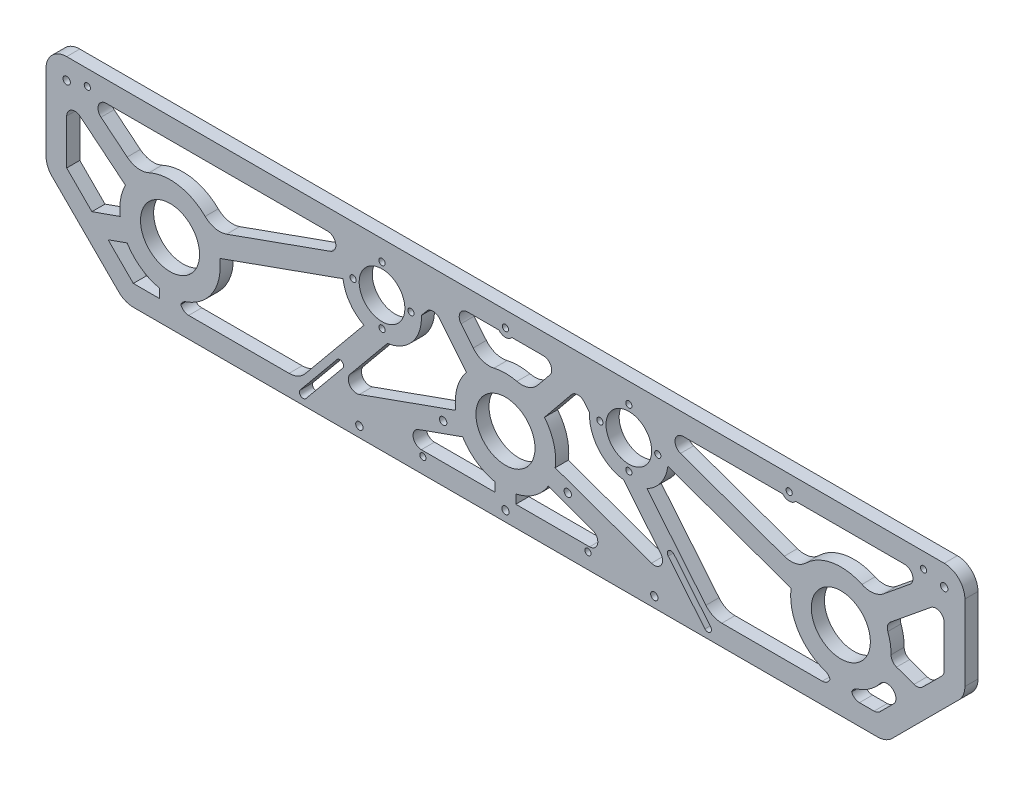
SolidWorks part; units mm, degrees
material "6061 Alloy"
ref_plane "Front Plane" through (0, 0, 0) normal (0, 0, 1) x (1, 0, 0)
ref_plane "Top Plane" through (0, 0, 0) normal (0, 1, 0) x (1, 0, 0)
ref_plane "Right Plane" through (0, 0, 0) normal (1, 0, 0) x (0, 0, -1)
sketch "Sketch1" plane through (0, 0, 0) normal (0, 0, 1) x (1, 0, 0)
  line L0 (2.9289, 35.1711) -> (35.1711, 2.9289)
  line L1 (42.2421, 0) -> (402.2579, 0)
  line L2 (0, 42.2421) -> (0, 78.9)
  line L3 (10, 88.9) -> (434.5, 88.9)
  line L4 (444.5, 42.2421) -> (444.5, 78.9)
  line L5 (409.3289, 2.9289) -> (441.5711, 35.1711)
  line L6 (222.25, 88.9) -> (222.25, 78.9) construction
  line L7 (42.2421, 10) -> (55, 10)
  line L8 (402.2579, 10) -> (414.4609, 22.2031)
  line L9 (434.5, 42.2421) -> (434.5, 72.4466)
  line L10 (17.9086, 78.9) -> (159.3033, 78.9)
  line L11 (10, 42.2421) -> (10, 72.4466)
  line L12 (10, 42.2421) -> (22.2031, 30.0391)
  line L13 (24.4543, 30.8351) -> (22.2031, 30.0391)
  line L14 (30.0391, 22.2031) -> (42.2421, 10)
  line L15 (10, 42.2421) -> (42.2421, 10) construction
  line L16 (44.7466, 57.0002) -> (17.9086, 78.9)
  line L17 (30.0391, 22.2031) -> (39.259, 25.463)
  line L18 (55, 14.3327) -> (55, 10)
  line L19 (38.4244, 49.2523) -> (10, 72.4466)
  line L20 (24.4543, 30.8351) -> (35.9254, 34.891)
  line L21 (65, 14.3327) -> (65, 10)
  line L22 (399.7534, 57.0002) -> (426.5914, 78.9)
  line L23 (65, 10) -> (128.7681, 10)
  line L24 (10, 78.9) -> (434.5, 78.9) construction
  line L25 (42.2421, 10) -> (402.2579, 10) construction
  line L26 (10, 42.2421) -> (10, 78.9) construction
  line L27 (185.1403, 75.7423) -> (203.3633, 53.37)
  line L28 (175.8429, 74.1917) -> (184.0222, 77.1149)
  line L29 (80.6981, 50.8071) -> (159.3033, 78.9)
  line L30 (84.0636, 41.3904) -> (175.8429, 74.1917)
  line L31 (158.4819, 10) -> (201.5519, 25.3929)
  line L32 (141.9423, 14.7083) -> (198.1864, 34.8096)
  line L33 (195.4658, 78.9) -> (211.1167, 59.6855)
  line L34 (185.1403, 75.7423) -> (184.0222, 77.1149)
  line L35 (406.0756, 49.2523) -> (434.5, 72.4466)
  line L36 (195.4658, 78.9) -> (249.0342, 78.9)
  line L37 (158.4819, 10) -> (217.25, 10)
  line L38 (217.25, 14.3327) -> (217.25, 10)
  line L39 (141.9423, 14.7083) -> (128.7681, 10)
  line L40 (420.0457, 30.8351) -> (422.2969, 30.0391)
  line L41 (420.0457, 30.8351) -> (408.5746, 34.891)
  line L42 (379.5, 14.3327) -> (379.5, 10)
  line L43 (389.5, 14.3327) -> (389.5, 10)
  line L44 (414.4609, 22.2031) -> (405.241, 25.463)
  line L45 (414.4609, 22.2031) -> (402.2579, 10)
  line L46 (402.2579, 10) -> (389.5, 10)
  line L47 (379.5, 10) -> (315.7319, 10)
  line L48 (286.0181, 10) -> (227.25, 10)
  line L49 (302.5577, 14.7083) -> (315.7319, 10)
  line L50 (302.5577, 14.7083) -> (246.3136, 34.8096)
  line L51 (286.0181, 10) -> (242.9481, 25.3929)
  line L52 (363.8019, 50.8071) -> (285.1967, 78.9)
  line L53 (360.4364, 41.3904) -> (268.6571, 74.1917)
  line L54 (268.6571, 74.1917) -> (260.4778, 77.1149)
  line L55 (259.3597, 75.7423) -> (260.4778, 77.1149)
  line L56 (249.0342, 78.9) -> (233.3833, 59.6855)
  line L57 (259.3597, 75.7423) -> (241.1367, 53.37)
  line L58 (285.1967, 78.9) -> (426.5914, 78.9)
  line L59 (422.2969, 30.0391) -> (434.5, 42.2421)
  line L60 (402.2579, 10) -> (434.5, 42.2421) construction
  line L61 (434.5, 42.2421) -> (434.5, 78.9) construction
  line L62 (227.25, 10) -> (227.25, 14.3327)
  arc A0 (434.5, 88.9) -> (444.5, 78.9) centre (434.5, 78.9) cw
  arc A1 (441.5711, 35.1711) -> (444.5, 42.2421) centre (434.5, 42.2421) ccw
  arc A2 (409.3289, 2.9289) -> (402.2579, 0) centre (402.2579, 10) cw
  arc A3 (35.1711, 2.9289) -> (42.2421, 0) centre (42.2421, 10) ccw
  arc A4 (2.9289, 35.1711) -> (0, 42.2421) centre (10, 42.2421) cw
  arc A5 (0, 78.9) -> (10, 88.9) centre (10, 78.9) cw
  circle A6 centre (60, 38.1) radius 14.2875
  circle A8 centre (384.5, 38.1) radius 14.2875
  arc A9 (402.2579, 10) -> (402.2579, 10) centre (402.2579, 10) cw
  arc A10 (434.5, 42.2421) -> (434.5, 42.2421) centre (434.5, 42.2421) ccw
  arc A11 (434.5, 78.9) -> (434.5, 78.9) centre (434.5, 78.9) cw
  arc A12 (10, 78.9) -> (10, 78.9) centre (10, 78.9) cw
  arc A13 (10, 42.2421) -> (10, 42.2421) centre (10, 42.2421) cw
  arc A14 (42.2421, 10) -> (42.2421, 10) centre (42.2421, 10) ccw
  arc A15 (38.4244, 49.2523) -> (35.9254, 34.891) centre (60, 38.1) ccw
  arc A16 (201.5519, 25.3929) -> (217.25, 14.3327) centre (222.25, 38.1) ccw
  arc A17 (363.8019, 50.8071) -> (399.7534, 57.0002) centre (384.5, 38.1) cw
  circle A18 centre (60, 38.1) radius 24.2875 construction
  arc A19 (39.259, 25.463) -> (55, 14.3327) centre (60, 38.1) ccw
  arc A20 (65, 14.3327) -> (84.0636, 41.3904) centre (60, 38.1) ccw
  arc A21 (80.6981, 50.8071) -> (44.7466, 57.0002) centre (60, 38.1) ccw
  circle A22 centre (222.25, 38.1) radius 14.2875
  arc A23 (203.3633, 53.37) -> (198.1864, 34.8096) centre (222.25, 38.1) ccw
  arc A24 (227.25, 14.3327) -> (242.9481, 25.3929) centre (222.25, 38.1) ccw
  arc A25 (246.3136, 34.8096) -> (241.1367, 53.37) centre (222.25, 38.1) ccw
  arc A26 (233.3833, 59.6855) -> (211.1167, 59.6855) centre (222.25, 38.1) ccw
  circle A27 centre (384.5, 38.1) radius 24.2875 construction
  arc A28 (406.0756, 49.2523) -> (408.5746, 34.891) centre (384.5, 38.1) cw
  arc A29 (379.5, 14.3327) -> (360.4364, 41.3904) centre (384.5, 38.1) cw
  arc A30 (405.241, 25.463) -> (389.5, 14.3327) centre (384.5, 38.1) cw
  point P0 (0, 0)
  point P3 (444.5, 0)
  point P13 (444.5, 38.1)
  point P16 (406.4, 0)
  point P19 (38.1, 0)
  point P22 (0, 38.1)
  point P25 (0, 88.9)
  dimension "D3" = 10
  dimension "D4" = 28.575
  dimension "D5" = 28.575
  dimension "D1" = 88.9
  dimension "D2" = 444.5
  dimension "D8" = 60
  dimension "D9" = 10
  dimension "D10" = 10
  dimension "D11" = 10
extrude "Boss-Extrude1" add sketch "Sketch1" along normal blind 6.35 contours A5 L2 A4 L0 A3 L1 A2 L5 A1 L4 A0 L3 A30 L44 L8 L46 L43 A29 L42 L47 L49 L50 A25 L57 L55 L54 L53 A28 L35 L9 L59 L40 L41 A22 A17 L52 L58 L22 A6 A8 L19 A15 L20 region at (4.9492, 40.15, 0)
sketch "Sketch2" plane through (0, 0, 6.35) normal (0, 0, 1) x (1, 0, 0)
  line L0 (65, 10) -> (128.7681, 10) construction
  line L1 (128.7681, 10) -> (198.1864, 34.8096) construction
  line L2 (257.2568, 73.1606) -> (306.5554, 13.2796)
  line L3 (174.8458, 73.8353) -> (124.908, 13.178)
  line L4 (269.6542, 73.8353) -> (319.592, 13.178)
  line L5 (187.8824, 73.937) -> (137.9446, 13.2796)
  line L6 (184.0222, 77.1149) -> (203.3633, 53.37) construction
  line L7 (84.0636, 41.3904) -> (184.0222, 77.1149) construction
  line L8 (122.2917, 10) -> (128.7681, 10)
  line L9 (128.7681, 10) -> (137.9446, 13.2796)
  line L10 (184.0222, 77.1149) -> (187.2432, 73.1606)
  line L11 (174.8458, 73.8353) -> (184.0222, 77.1149)
  line L12 (124.908, 13.178) -> (122.2917, 10)
  line L13 (319.592, 13.178) -> (322.2083, 10)
  line L14 (246.3136, 34.8096) -> (315.7319, 10) construction
  line L15 (379.5, 10) -> (315.7319, 10) construction
  line L16 (260.4778, 77.1149) -> (241.1367, 53.37) construction
  line L17 (360.4364, 41.3904) -> (260.4778, 77.1149) construction
  line L18 (306.5554, 13.2796) -> (315.7319, 10)
  line L19 (322.2083, 10) -> (315.7319, 10)
  line L20 (260.4778, 77.1149) -> (257.2568, 73.1606)
  line L21 (269.6542, 73.8353) -> (260.4778, 77.1149)
extrude "Boss-Extrude2" add sketch "Sketch2" against normal up to surface (6.35 mm away) contours L3 L12 L8 L9 L5 L10 L11 | L4 L21 L20 L2 L18 L19 L13 region at (288.5779, 43.0632, 6.35) region at (155.9221, 43.0632, 6.35) up to face at (400.4223, 16.074, 0)
fillet "Fillet1" radius 10 8 edges at (80.6981, 50.8071, 3.175) (44.7466, 57.0002, 3.175) (211.1167, 59.6855, 3.175) (233.3833, 59.6855, 3.175) (122.2917, 10, 3.175) (322.2083, 10, 3.175) (399.7534, 57.0002, 3.175) (363.8019, 50.8071, 3.175)
fillet "Fillet2" radius 4 16 edges at (10, 72.4466, 3.175) (434.5, 72.4466, 3.175) (17.9086, 78.9, 3.175) (159.3033, 78.9, 3.175) (174.8458, 73.8353, 3.175) (269.6542, 73.8353, 3.175) (286.0181, 10, 3.175) (158.4819, 10, 3.175) (137.9446, 13.2796, 3.175) (306.5554, 13.2796, 3.175) (257.2568, 73.1606, 3.175) (187.2432, 73.1606, 3.175) (195.4658, 78.9, 3.175) (249.0342, 78.9, 3.175) (426.5914, 78.9, 3.175) (285.1967, 78.9, 3.175)
fillet "Fillet3" radius 4 13 edges at (434.5, 42.2421, 3.175) (422.2969, 30.0391, 3.175) (408.5746, 34.891, 3.175) (406.0756, 49.2523, 3.175) (414.4609, 22.2031, 3.175) (405.241, 25.463, 3.175) (402.2579, 10, 3.175) (389.5, 10, 3.175) (389.5, 14.3327, 3.175) (65, 10, 3.175) (65, 14.3327, 3.175) (379.5, 14.3327, 3.175) (379.5, 10, 3.175)
sketch "Sketch3" plane through (0, 0, 0) normal (0, 0, -1) x (-1, 0, 0)
  line L0 (-222.25, 88.9) -> (-222.25, 78.9) construction
  line L1 (-10, 88.9) -> (-434.5, 88.9) construction
  line L2 (-203.8829, 78.9) -> (-240.6171, 78.9) construction
  circle A0 centre (-434.5, 78.9) radius 1.778
  circle A2 centre (-252.3834, 27.3306) radius 1.778
  circle A3 centre (-192.1166, 27.3306) radius 1.778
  circle A4 centre (-10, 78.9) radius 1.778
  circle A5 centre (-222.25, 38.1) radius 14.2875 construction
  dimension "D1" = 3.556
  dimension "D2" = 3.556
  dimension "D3" = 3.556
  dimension "D5" = 32
  dimension "D4" = 32
extrude "Cut-Extrude1" cut sketch "Sketch3" against normal blind 10
sketch "Sketch4" plane through (0, 0, 0) normal (0, 0, -1) x (-1, 0, 0)
  line L0 (-222.25, 88.9) -> (-222.25, 78.9) construction
  line L3 (-10, 88.9) -> (-434.5, 88.9) construction
  line L4 (-302.3362, 26.2712) -> (-320.1327, 4.6545) construction
  line L5 (-300.9635, 25.1411) -> (-318.76, 3.5244)
  line L6 (-303.7088, 27.4013) -> (-321.5054, 5.7846)
  line L7 (-203.8829, 78.9) -> (-240.6171, 78.9) construction
  line L8 (-142.1638, 26.2712) -> (-124.3673, 4.6545) construction
  line L9 (-143.5365, 25.1411) -> (-125.74, 3.5244)
  line L10 (-140.7912, 27.4013) -> (-122.9946, 5.7846)
  arc A0 (-300.9635, 25.1411) -> (-303.7088, 27.4013) centre (-302.3362, 26.2712) ccw
  arc A1 (-321.5054, 5.7846) -> (-318.76, 3.5244) centre (-320.1327, 4.6545) ccw
  arc A2 (-143.5365, 25.1411) -> (-140.7912, 27.4013) centre (-142.1638, 26.2712) cw
  arc A3 (-122.9946, 5.7846) -> (-125.74, 3.5244) centre (-124.3673, 4.6545) cw
  point P10 (-311.2344, 15.4628)
  point P15 (-133.2656, 15.4628)
extrude "Cut-Extrude2" cut sketch "Sketch4" against normal blind 10
sketch "Sketch6" plane through (0, 0, 0) normal (0, 0, -1) x (-1, 0, 0)
  line L0 (-222.25, 88.9) -> (-222.25, 78.9) construction
  line L1 (-10, 88.9) -> (-434.5, 88.9) construction
  line L2 (-203.8829, 78.9) -> (-240.6171, 78.9) construction
  circle A0 centre (-281.9505, 65.1929) radius 11.049
  circle A2 centre (-281.9505, 79.1883) radius 1.5
  circle A3 centre (-281.9505, 65.1929) radius 19.05
  circle A4 centre (-267.9551, 65.1929) radius 1.5
  circle A5 centre (-281.9505, 51.1975) radius 1.5
  circle A6 centre (-295.9459, 65.1929) radius 1.5
  circle A7 centre (-148.5541, 65.1929) radius 1.5
  circle A8 centre (-162.5495, 51.1975) radius 1.5
  circle A9 centre (-176.5449, 65.1929) radius 1.5
  circle A10 centre (-162.5495, 65.1929) radius 19.05
  circle A11 centre (-162.5495, 79.1883) radius 1.5
  circle A12 centre (-162.5495, 65.1929) radius 11.049
  point P15 (-281.9505, 65.1929)
  dimension "D1" = 22.098
  dimension "D2" = 4
  dimension "D3" = 3
  dimension "D4" = 38.1
extrude "Boss-Extrude3" add sketch "Sketch6" against normal up to surface (6.35 mm away) up to face at (311.2344, 15.4628, 6.35)
extrude "Cut-Extrude4" cut sketch "Sketch6<5>" against normal blind 10 contours A12 | A11 | A9 | A8 | A0 | A2 | A6 | A5 | A7 | A4 region at (281.9505, 65.1929, 0) region at (281.9505, 79.1883, 0) region at (281.9505, 51.1975, 0) region at (295.9459, 65.1929, 0) region at (162.5495, 51.1975, 0) region at (176.5449, 65.1929, 0) region at (162.5495, 79.1883, 0) region at (162.5495, 65.1929, 0)
sketch "Sketch6<5>" plane through (0, 0, 0) normal (0, 0, -1) x (-1, 0, 0) same geometry as "Sketch6"
sketch "Sketch7" plane through (0, 0, 6.35) normal (0, 0, 1) x (1, 0, 0)
  circle A0 centre (222.25, 5) radius 1.778
  dimension "D2" = 3.556
extrude "Cut-Extrude5" cut sketch "Sketch7" against normal blind 10
sketch "Sketch8" plane through (0, 0, 6.35) normal (0, 0, 1) x (1, 0, 0)
  line L0 (42.2421, 0) -> (402.2579, 0) construction
  circle A0 centre (151.587, 5) radius 1.778
  circle A1 centre (294.2591, 5) radius 1.778
  dimension "D1" = 3.556
  dimension "D2" = 5
  dimension "D3" = 3.556
extrude "Cut-Extrude6" cut sketch "Sketch8" against normal blind 10
sketch "Sketch9" plane through (0, 0, 0) normal (0, 0, -1) x (-1, 0, 0)
  line L0 (-10, 88.9) -> (-434.5, 88.9) construction
  line L1 (-444.5, 42.2421) -> (-444.5, 78.9) construction
  line L2 (-222.25, 88.9) -> (-222.25, 78.9) construction
  line L3 (-203.8829, 78.9) -> (-240.6171, 78.9) construction
  line L4 (-42.2421, 0) -> (-402.2579, 0) construction
  circle A0 centre (-424.5, 81.4) radius 1.5
  circle A1 centre (-262.1718, 7.5) radius 1.5
  circle A2 centre (-222.25, 5) radius 1.778 construction
  circle A4 centre (-182.3282, 7.5) radius 1.5
  circle A5 centre (-20, 81.4) radius 1.5
  circle A6 centre (-222.25, 81.4) radius 1.5
  dimension "D1" = 3
  dimension "D2" = 7.5
  dimension "D3" = 20
  dimension "D4" = 3
  dimension "D6" = 3
  dimension "D7" = 7.5
  dimension "D5" = 40
  dimension "D8" = 7.5
extrude "Cut-Extrude7" cut sketch "Sketch9" against normal blind 10
sketch "Sketch10" plane through (0, 0, 0) normal (0, 0, -1) x (-1, 0, 0)
  line L0 (-444.5, 42.2421) -> (-444.5, 78.9) construction
  line L2 (-10, 88.9) -> (-434.5, 88.9) construction
  circle A0 centre (-359.5, 81.4) radius 1.5
  circle A1 centre (-359.5, 81.4) radius 4
  circle A2 centre (-222.25, 81.4) radius 4
  circle A3 centre (-222.25, 81.4) radius 1.5
  dimension "D1" = 3
  dimension "D3" = 7.5
  dimension "D4" = 8
  dimension "D5" = 8
  dimension "D2" = 85
extrude "Boss-Extrude4" add sketch "Sketch10" against normal through all
extrude "Cut-Extrude8" cut sketch "Sketch10<4>" against normal blind 10 contours A0
sketch "Sketch10<4>" plane through (0, 0, 0) normal (0, 0, -1) x (-1, 0, 0) same geometry as "Sketch10"
